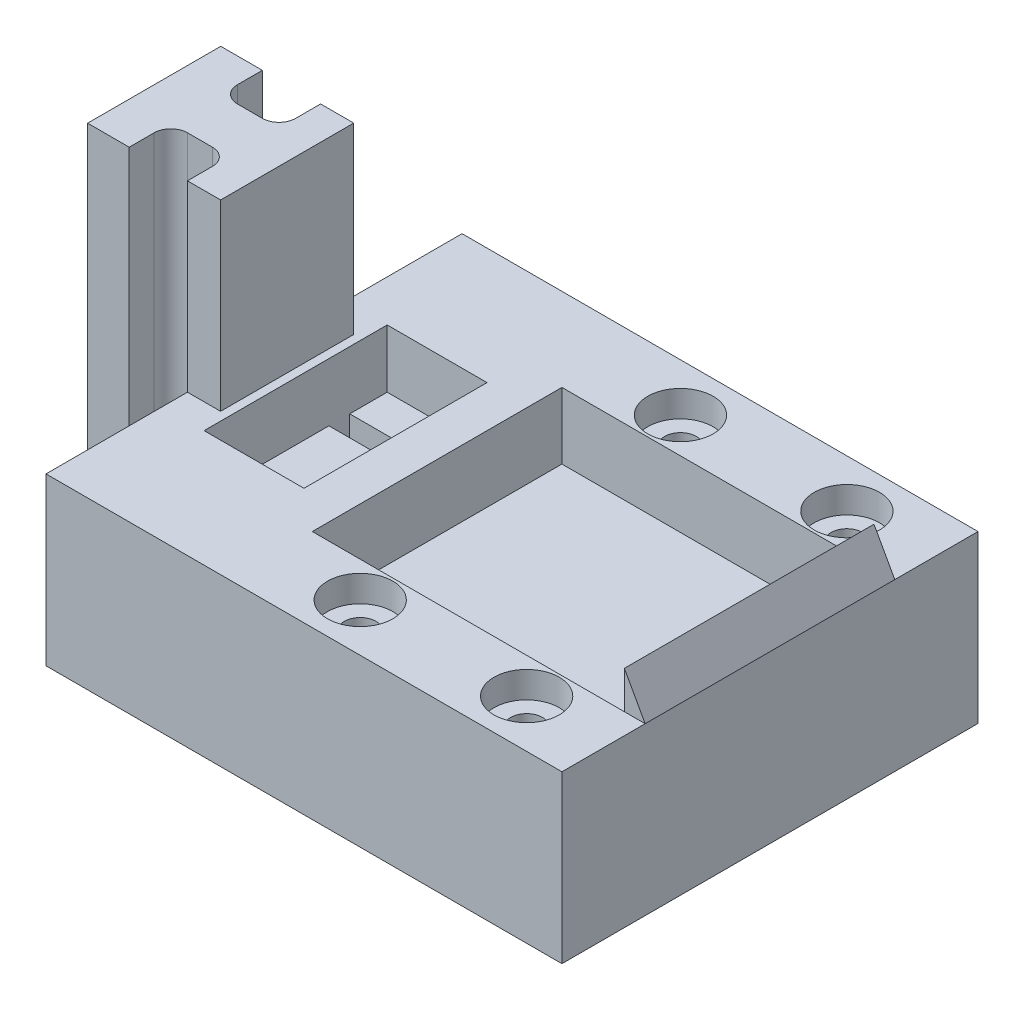
SolidWorks part; units mm, degrees
ref_plane "Front Plane" through (0, 0, 0) normal (0, 0, 1) x (1, 0, 0)
ref_plane "Top Plane" through (0, 0, 0) normal (0, 1, 0) x (1, 0, 0)
ref_plane "Right Plane" through (0, 0, 0) normal (1, 0, 0) x (0, 0, -1)
sketch "Sketch1" plane through (0, 0, 0) normal (0, 0, 1) x (1, 0, 0)
  circle A0 centre (0, 0) radius 17.5
  dimension "D1" = 35
extrude "Boss-Extrude1" add sketch "Sketch1" along normal blind 30
sketch "Sketch5" plane through (0, 0, 0) normal (0, 0, -1) x (-1, 0, 0)
  circle A0 centre (0, 0) radius 10.95
  dimension "D1" = 21.9
extrude "Cut-Extrude2" cut sketch "Sketch5" against normal through all
ref_plane "Plane1" through (0, 0, -10) normal (0, 0, -1) x (-1, 0, 0)
sketch "Sketch6" plane through (0, 0, -10) normal (0, 0, -1) x (-1, 0, 0)
  circle A0 centre (0, 0) radius 10.95 construction
  circle A1 centre (0, 0) radius 10.95
curve "Helix/Spiral2" pitch 10 height 40 turns 4
sketch "Sketch7" plane through (0, 0, 0) normal (1, 0, 0) x (0, 0, -1)
  line L0 (7.5, -6.95) -> (7.5, -10.95) construction
  line L1 (7.067, -7.7) -> (5.1906, -10.95)
  line L2 (5.1906, -10.95) -> (9.8094, -10.95)
  line L3 (7.933, -7.7) -> (9.8094, -10.95)
  arc A0 (7.933, -7.7) -> (7.067, -7.7) centre (7.5, -7.95) ccw
  dimension "D3" = 0.5
  dimension "D1" = 60
  dimension "D2" = 4
sweep "Sweep2" add profiles "Sketch7" path "Helix/Spiral2"
sketch "Sketch8" plane through (0, 0, 0) normal (0, 0, -1) x (-1, 0, 0)
  circle A0 centre (0, 0) radius 17.5
  circle A1 centre (0, 0) radius 17.5 construction
extrude "Cut-Extrude3" cut sketch "Sketch8" along normal through all
sketch "Sketch9" plane through (0, 0, 30) normal (0, 0, 1) x (1, 0, 0)
  circle A0 centre (0, 0) radius 17.5
  circle A1 centre (0, 0) radius 17.5 construction
extrude "Cut-Extrude4" cut sketch "Sketch9" along normal through all
sketch "Sketch10" plane through (0, 0, 0) normal (0, 0, -1) x (-1, 0, 0)
  line L0 (-20, -17.5) -> (0, 0) construction
  line L1 (-20, -17.5) -> (20, -17.5)
  line L2 (-20, -17.5) -> (-20, -37.4773)
  line L3 (-20, -37.4773) -> (20, -37.4773)
  line L4 (20, -17.5) -> (20, -37.4773)
  line L5 (0, 0) -> (20, -17.5) construction
  circle A0 centre (0, 0) radius 17.5 construction
  dimension "D1" = 40
  dimension "D2" = 19.9773
extrude "Boss-Extrude2" add sketch "Sketch10" against normal blind 40 separate body
sketch "Sketch11" plane through (0, 0, 0) normal (0, 0, -1) x (-1, 0, 0)
  line L1 (-20, -17.5) -> (20, -17.5)
  line L2 (-20, -17.5) -> (-20, -37.4773)
  line L3 (-20, -37.4773) -> (20, -37.4773)
  line L4 (20, -17.5) -> (20, -37.4773)
extrude "Boss-Extrude3" add sketch "Sketch11" along normal blind 10
sketch "Sketch13" plane through (0, 0, 0) normal (0, 0, -1) x (-1, 0, 0)
  line L0 (0, -17.5) -> (-20, -17.5)
  line L1 (20, -17.5) -> (-20, -17.5) construction
  line L2 (-20, -17.5) -> (-15.1539, -8.7527)
  circle A0 centre (0, 0) radius 17.5 construction
  arc A1 (-15.1539, -8.7527) -> (0, -17.5) centre (0, 0) ccw
  dimension "D1" = 10
extrude "Boss-Extrude4" add sketch "Sketch13" against normal up to surface (30 mm away) up to face at (-3.7285, 0.054, 30)
ref_plane "Plane2" through (0, 0, 0) normal (1, 0, 0) x (0, 0, -1)
mirror "Mirror1" about plane through (0, 0, 0) normal (1, 0, 0) of "Boss-Extrude4"
sketch "Sketch14" plane through (0, -37.4773, 0) normal (0, -1, 0) x (1, 0, 0)
  line L0 (-20, 40) -> (20, -10) construction
  line L2 (-20, -10) -> (20, 40) construction
  line L3 (10, -4.2426) -> (-10, -4.2426) construction
  line L4 (10, -4.2426) -> (10, 34.2426) construction
  line L5 (10, 34.2426) -> (-10, 34.2426) construction
  line L6 (-10, -4.2426) -> (-10, 34.2426) construction
  line L7 (10, -4.2426) -> (-10, 34.2426) construction
  line L8 (10, 34.2426) -> (-10, -4.2426) construction
  circle A0 centre (-10, 34.2426) radius 1.905
  circle A1 centre (10, 34.2426) radius 1.905
  circle A2 centre (-10, -4.2426) radius 1.905
  circle A3 centre (10, -4.2426) radius 1.905
  point P8 (0, 15)
  dimension "D3" = 3.81
  dimension "D1" = 38.4853
  dimension "D2" = 20
extrude "Cut-Extrude5" cut sketch "Sketch14" against normal through all
ref_plane "Plane3" through (0, -20.6734, 0) normal (0, 1, 0) x (1, 0, 0)
sketch "Sketch15" plane through (0, -20.6734, 0) normal (0, 1, 0) x (1, 0, 0)
  circle A0 centre (-10, 4.2426) radius 3.9243
  circle A1 centre (10, 4.2426) radius 3.9243
  circle A2 centre (10, -34.2426) radius 3.9243
  circle A3 centre (-10, -34.2426) radius 3.9243
  dimension "D1" = 7.8486
extrude "Cut-Extrude7" cut sketch "Sketch15" along normal through all
sketch "Sketch16" plane through (-20, 0, 0) normal (-1, 0, 0) x (0, 0, 1)
  line L0 (40, -37.4773) -> (40, -17.5) construction
  line L1 (-10, -17.5) -> (40, -17.5)
  line L2 (-10, -17.5) -> (-10, -37.4773)
  line L3 (-10, -37.4773) -> (40, -37.4773)
  line L4 (40, -17.5) -> (40, -37.4773)
  line L5 (40, -37.4773) -> (-10, -37.4773) construction
extrude "Boss-Extrude5" add sketch "Sketch16" along normal blind 22
ref_plane "Plane4" through (-37, 0, 0) normal (-1, 0, 0) x (0, 0, 1)
sketch "Sketch17" plane through (-37, 0, 0) normal (-1, 0, 0) x (0, 0, 1)
  line L0 (40, -17.5) -> (-10, -17.5) construction
  line L5 (4, -24.5) -> (-10, -17.5) construction
  line L6 (40, -17.5) -> (26, -24.5) construction
  line L12 (4, -24.5) -> (8.5, -24.5)
  line L13 (11, -24.5) -> (26, -24.5)
  line L14 (26, -17.5) -> (4, -17.5)
  line L15 (4, -17.5) -> (4, -24.5)
  line L16 (26, -17.5) -> (26, -24.5)
  line L17 (8.5, -24.5) -> (8.5, -29.4889)
  line L18 (11, -24.5) -> (11, -29.4889)
  line L19 (8.5, -29.4889) -> (11, -29.4889)
  dimension "D1" = 22
  dimension "D2" = 7
  dimension "D3" = 2.5
  dimension "D4" = 4.5
extrude "Cut-Extrude8" cut sketch "Sketch17" against normal blind 12
sketch "Sketch19" plane through (0, -17.5, 0) normal (0, 1, 0) x (1, 0, 0)
  line L0 (-42, -40) -> (-42, 10) construction
  line L1 (-42, -12) -> (-49, -12)
  line L2 (-42, -12) -> (-42, -18)
  line L3 (-42, -18) -> (-49, -18)
  line L5 (-54, -12) -> (-37, -4) construction
  line L6 (-54, -18) -> (-37, -26) construction
  line L7 (-49, -7) -> (-37, -4) construction
  line L8 (-54, -7) -> (-49, -7)
  line L10 (-54, -23) -> (-49, -23)
  line L11 (-49, -7) -> (-49, -12)
  line L12 (-49, -23) -> (-37, -26) construction
  line L13 (-49, -18) -> (-49, -23)
  line L14 (-54, -7) -> (-54, -23)
  dimension "D1" = 6
  dimension "D2" = 16
  dimension "D3" = 7
  dimension "D4" = 12
extrude "Boss-Extrude6" add sketch "Sketch19" against normal through all
sketch "Sketch20" plane through (0, -17.5, 0) normal (0, 1, 0) x (1, 0, 0)
  line L0 (-42, -12) -> (-42, 10) construction
  line L1 (-54, -7) -> (-49, -7)
  line L2 (-54, -7) -> (-54, -23)
  line L3 (-54, -23) -> (-49, -23)
  line L4 (-49, -7) -> (-49, -12)
  line L5 (-42, -12) -> (-49, -12)
  line L7 (-42, -18) -> (-49, -18)
  line L9 (-42, -7) -> (-38.0182, -7)
  line L10 (-42, -7) -> (-42, -12)
  line L11 (-42, -23) -> (-38.0182, -23)
  line L14 (-42, -18) -> (-42, -23)
  line L15 (-49, -18) -> (-49, -23)
  line L16 (-38.0182, -7) -> (-38.0182, -23)
extrude "Boss-Extrude7" add sketch "Sketch20" along normal blind 22
fillet "Fillet1" radius 2 4 edges at (-42, -16.4886, 12) (-42, -16.4886, 18) (-49, -16.4886, 18) (-49, -16.4886, 12)
sketch "Sketch21" plane through (0, -37.4773, 0) normal (0, -1, 0) x (1, 0, 0)
  line L0 (-42, -10) -> (-42, 10) construction
  line L1 (-49, 23) -> (-42, 23)
  line L2 (-49, 23) -> (-49, 7)
  line L3 (-49, 7) -> (-42, 7)
  line L4 (-42, 23) -> (-42, 7)
  line L5 (-49, 7) -> (-54, 7) construction
extrude "Boss-Extrude8" add sketch "Sketch21" against normal blind 2
sketch "Sketch22" plane through (0, -17.5, 0) normal (0, 1, 0) x (1, 0, 0)
  line L5 (-20, 0) -> (17.5, 0)
  line L6 (-20, 0) -> (-20, -30)
  line L7 (-20, -30) -> (17.5, -30)
  line L8 (17.5, 0) -> (17.5, -30)
extrude "Cut-Extrude9" cut sketch "Sketch22" against normal through all and the other way through all
sketch "Sketch24" plane through (0, -37.4773, 0) normal (0, -1, 0) x (1, 0, 0)
  line L1 (-20, 30) -> (17.5, 30)
  line L2 (-20, 30) -> (-20, 0)
  line L3 (-20, 0) -> (17.5, 0)
  line L4 (17.5, 30) -> (17.5, 0)
extrude "Boss-Extrude9" add sketch "Sketch24" against normal blind 12
